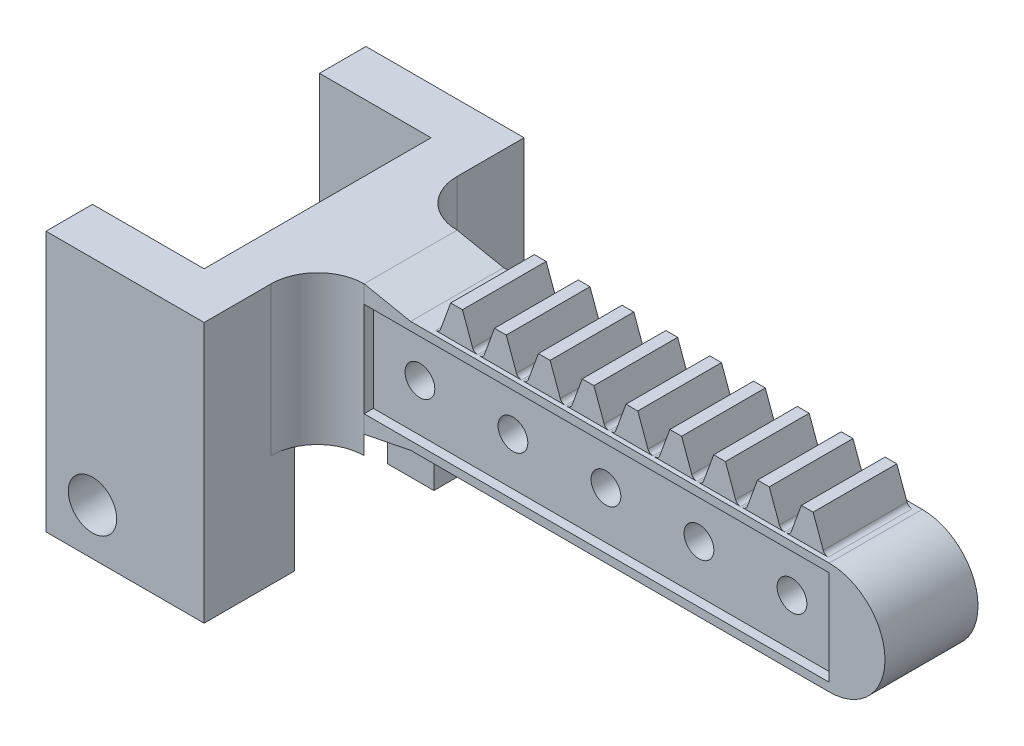
SolidWorks part; units mm, degrees
ref_plane "Front Plane" through (0, 0, 0) normal (0, 0, 1) x (1, 0, 0)
ref_plane "Top Plane" through (0, 0, 0) normal (0, 1, 0) x (1, 0, 0)
ref_plane "Right Plane" through (0, 0, 0) normal (1, 0, 0) x (0, 0, -1)
sketch "Esquisse1" plane through (0, 0, 0) normal (0, 0, 1) x (1, 0, 0)
  line L0 (-22.5, 6) -> (-27.5, 7)
  line L1 (-22.5, 6) -> (22.5, 6)
  line L2 (-27.5, 7) -> (-32.5, 7)
  line L3 (-22.5, -6) -> (22.5, -6)
  line L4 (-32.5, 7) -> (-32.5, -7)
  line L5 (-32.5, -7) -> (-27.5, -7)
  line L6 (-27.5, -7) -> (-22.5, -6)
  line L7 (18.92, 0) -> (-18.92, 0) construction
  arc A0 (22.5, 6) -> (22.5, -6) centre (22.5, 0) cw
  point P6 (0, -6)
  point P13 (-32.5, 0)
  dimension "D1" = 12
  dimension "D2" = 45
  dimension "D3" = 14
  dimension "D4" = 5
  dimension "D5" = 5
extrude "Main Extrusion" add sketch "Esquisse1" along normal mid plane 10
sketch "Esquisse5" plane through (0, 0, 0) normal (0, 0, 1) x (1, 0, 0)
  line L0 (17.7789, 6) -> (19.0073, 9.375)
  line L1 (19.0073, 9.375) -> (20.2716, 9.375)
  line L2 (20.2716, 9.375) -> (21.5, 6)
  line L3 (17.7789, 6) -> (16.7876, 6) construction
  line L4 (17.7789, 6) -> (21.5, 6)
  line L5 (22.5, 6) -> (-22.5, 6) construction
  line L6 (17.9154, 6.375) -> (16.6511, 6.375) construction
  line L7 (17.7789, 6) -> (17.7789, 8.8688) construction
  line L9 (16.7876, 6) -> (16.505, 6.7765) construction
  line L10 (16.1052, 7.875) -> (20.8176, 7.875) construction
  dimension "D1" = 20
  dimension "D2" = 1.5
  dimension "h" = 3.375
  dimension "p" = 4.7124
  dimension "hw" = 3
  dimension "D3" = 1
extrude "Tooth" add sketch "Esquisse5" along normal mid plane 9
fillet "Tooth Fillet" radius 0.57 2 edges at (17.7789, 6, 0) (21.5, 6, 0)
pattern_linear "ToothRepeat" count 9 spacing 4.7124 along (-1, 0, 0) of "Tooth Fillet", "Tooth"
sketch "Esquisse10" plane through (0, 7, 0) normal (0, 1, 0) x (1, 0, 0)
  line L0 (-32.5, -5) -> (-32.5, 5) construction
  line L1 (-32.5, -17.2) -> (-49.5, -17.2)
  line L2 (-49.5, -17.2) -> (-49.5, -12.2)
  line L3 (-49.5, -12.2) -> (-37.5, -12.2)
  line L4 (-37.5, -12.2) -> (-37.5, 12.2)
  line L5 (-37.5, 12.2) -> (-49.5, 12.2)
  line L6 (-49.5, 12.2) -> (-49.5, 17.2)
  line L7 (-49.5, 17.2) -> (-32.5, 17.2)
  line L8 (-32.5, 17.2) -> (-32.5, -17.2)
  point P14 (-32.5, 0)
  point P15 (-32.5, 0)
  dimension "D1" = 24.4
  dimension "D2" = 5
  dimension "D3" = 5
  dimension "D4" = 12
extrude "FixingSupport" add sketch "Esquisse10" against normal blind 28 separate body
sketch "Esquisse11" plane through (0, 0, 17.2) normal (0, 0, 1) x (1, 0, 0)
  line L0 (-49.5, -21) -> (-49.5, 7) construction
  line L2 (-49.5, -21) -> (-32.5, -21) construction
  circle A0 centre (-44.5, -16) radius 2.6
  dimension "D1" = 5.2
  dimension "D2" = 5
  dimension "D3" = 5
extrude "FixingHoles" cut sketch "Esquisse11" against normal through all
sketch "Esquisse12" plane through (-32.5, 0, 0) normal (1, 0, 0) x (0, 0, -1)
  line L0 (-17.2, -21) -> (17.2, -21) construction
  line L1 (7.5, -9) -> (-7.5, -9)
  line L2 (7.5, -9) -> (7.5, -21)
  line L3 (7.5, -21) -> (-7.5, -21)
  line L4 (-7.5, -9) -> (-7.5, -21)
  point P7 (0, -21)
  point P8 (0, -21)
  dimension "D1" = 15
  dimension "D2" = 12
extrude "RackHole" cut sketch "Esquisse12" against normal through all
sketch "Esquisse14" plane through (0, 7, 0) normal (0, 1, 0) x (1, 0, 0)
  line L0 (-32.5, -5) -> (-32.5, -10)
  line L1 (-32.5, -17.2) -> (-32.5, 17.2) construction
  line L2 (-27.5, -5) -> (-32.5, -5) construction
  line L3 (-32.5, -5) -> (-27.5, -5)
  arc A0 (-27.5, -5) -> (-32.5, -10) centre (-27.5, -10) ccw
  dimension "D1" = 5
extrude "Fillet" add sketch "Esquisse14" against normal up to surface (16 mm away) up to face at (-35, -9, 0)
mirror "FilletSymetry" about plane through (0, 0, 0) normal (0, 0, 1) of "Fillet"
sketch "Esquisse15" plane through (0, 0, 5) normal (0, 0, 1) x (1, 0, 0)
  line L0 (-27.5, -7) -> (-27.5, 7) construction
  line L1 (-27.5, 5.1) -> (22.5, 5.1)
  line L2 (-27.5, 5.1) -> (-27.5, -5.1)
  line L3 (-27.5, -5.1) -> (22.5, -5.1)
  line L4 (22.5, 5.1) -> (22.5, -5.1)
  arc A0 (22.5, -6) -> (22.5, 6) centre (22.5, 0) ccw construction
  point P7 (28.5, 0)
  point P8 (22.5, 0)
  point P9 (-27.5, -5.1)
  dimension "D1" = 10.2
  dimension "D2" = 50
extrude "Reinforcement" cut sketch "Esquisse15" against normal blind 1
mirror "Symétrie1" about plane through (0, 0, 0) normal (0, 0, 1) of "Reinforcement"
sketch "Esquisse16" plane through (0, 0, 4) normal (0, 0, 1) x (1, 0, 0)
  line L0 (22.5, 5.1) -> (-27.5, 5.1) construction
  circle A0 centre (17.5, 0) radius 1.6
  circle A1 centre (7.5, 0) radius 1.6
  circle A2 centre (-2.5, 0) radius 1.6
  circle A3 centre (-12.5, 0) radius 1.6
  circle A4 centre (-22.5, 0) radius 1.6
  point P10 (0, 0)
  point P12 (0, 0)
  point P15 (-2.5, 5.1)
  dimension "D1" = 3.2
  dimension "D3" = 10
  dimension "D4" = 10
  dimension "D5" = 10
  dimension "D2" = 10
extrude "Enlèv. mat.-Extru.2" cut sketch "Esquisse16" against normal through all
equation "\"modulo\"= 1.5mm"
equation "\"h@Esquisse5\"= \"modulo\" * 2.25"
equation "\"D2@Esquisse5\"= \"modulo\""
equation "\"p@Esquisse5\"= \"modulo\" * pi"
equation "\"hw@Esquisse5\"= \"modulo\" * 2"
equation "\"0.5è\"=10"
